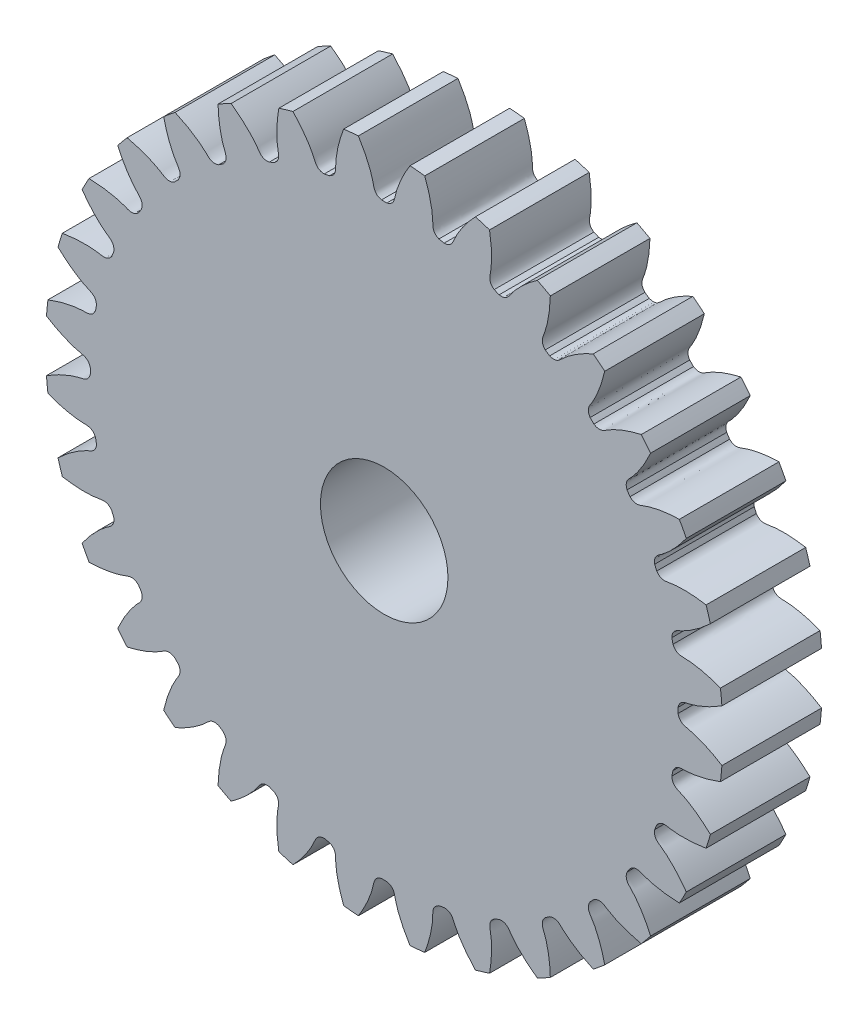
SolidWorks part; units mm, degrees
ref_plane "前视基准面" through (0, 0, 0) normal (0, 0, 1) x (1, 0, 0)
ref_plane "上视基准面" through (0, 0, 0) normal (0, 1, 0) x (1, 0, 0)
ref_plane "右视基准面" through (0, 0, 0) normal (1, 0, 0) x (0, 0, -1)
other "Configuration Table"
sketch "草图1" plane through (0, 0, 0) normal (0, 0, 1) x (1, 0, 0)
  circle A0 centre (0, 0) radius 8.5
extrude "凸台-拉伸1" add sketch "草图1" along normal blind 2.5
ref_axis "基准轴1" through (0, 0, 2.5) along (0, 0, -1)
sketch "草图2" plane through (0, 0, 0) normal (0, 0, 1) x (1, 0, 0)
  line L0 (0, 0) -> (0, 8.5) construction
  circle A0 centre (0, 0) radius 8.5 construction
  arc A1 (0.067, 7.3747) -> (-0.067, 7.3747) centre (0, 0) ccw
  arc A2 (1.6765, 9.6348) -> (-1.6765, 9.6348) centre (0, 0) ccw
  spline S0 degree 3 poles (0.067, 7.3747) (0.2444, 7.4176) (0.2542, 7.5462) (0.2867, 7.6804) (0.2952, 7.7127) (0.3051, 7.7477) (0.3166, 7.7854) (0.3299, 7.8257) (0.3449, 7.8686) (0.3618, 7.9139) (0.3807, 7.9618) (0.4017, 8.012) (0.4249, 8.0645) (0.4505, 8.1193) (0.4785, 8.1763) (0.509, 8.2353) (0.5421, 8.2964) (0.5779, 8.3594) (0.6164, 8.4243) (0.6579, 8.491) (0.7023, 8.5593) (0.7498, 8.6292) (0.8004, 8.7006) (0.8542, 8.7734) (0.9113, 8.8475) (0.9717, 8.9228) (1.0356, 8.9992) (1.1029, 9.0765) (1.1738, 9.1547) (1.2483, 9.2337) (1.3265, 9.3133) (1.4084, 9.3934) (1.5241, 9.5022) (1.6145, 9.5821) (1.6765, 9.6348) knots 0 0 0 0 0.124533 0.135329 0.147193 0.160126 0.174128 0.189198 0.205337 0.222544 0.24082 0.260164 0.280577 0.302059 0.324609 0.348227 0.372914 0.39867 0.425494 0.453386 0.482348 0.512377 0.543476 0.575642 0.608878 0.643181 0.678554 0.714995 0.752504 0.791082 0.830729 0.871444 0.913227 1 1 1 1
  spline S1 degree 3 poles (-0.067, 7.3747) (-0.2444, 7.4176) (-0.2542, 7.5462) (-0.2867, 7.6804) (-0.2952, 7.7127) (-0.3051, 7.7477) (-0.3166, 7.7854) (-0.3299, 7.8257) (-0.3449, 7.8686) (-0.3618, 7.9139) (-0.3807, 7.9618) (-0.4017, 8.012) (-0.4249, 8.0645) (-0.4505, 8.1193) (-0.4785, 8.1763) (-0.509, 8.2353) (-0.5421, 8.2964) (-0.5779, 8.3594) (-0.6164, 8.4243) (-0.6579, 8.491) (-0.7023, 8.5593) (-0.7498, 8.6292) (-0.8004, 8.7006) (-0.8542, 8.7734) (-0.9113, 8.8475) (-0.9717, 8.9228) (-1.0356, 8.9992) (-1.1029, 9.0765) (-1.1738, 9.1547) (-1.2483, 9.2337) (-1.3265, 9.3133) (-1.4084, 9.3934) (-1.5241, 9.5022) (-1.6145, 9.5821) (-1.6765, 9.6348) knots 0 0 0 0 0.124533 0.135329 0.147193 0.160126 0.174128 0.189198 0.205337 0.222544 0.24082 0.260164 0.280577 0.302059 0.324609 0.348227 0.372914 0.39867 0.425494 0.453386 0.482348 0.512377 0.543476 0.575642 0.608878 0.643181 0.678554 0.714995 0.752504 0.791082 0.830729 0.871444 0.913227 1 1 1 1
extrude "切除-拉伸1" cut sketch "草图2" along normal through all
pattern_circular "阵列(圆周)1" count 32 every 11.25 about axis through (0, 0, 2.5) along (0, 0, -1) of "切除-拉伸1"
sketch "草图3" plane through (0, 0, 0) normal (0, 0, 1) x (1, 0, 0)
  circle A0 centre (0, 0) radius 8 construction
  dimension "Dn" = 16
sketch "草图4" plane through (0, 0, 0) normal (0, 0, -1) x (-1, 0, 0)
  circle A0 centre (0, 0) radius 1.6
  dimension "D1" = 3.2
extrude "切除-拉伸2" cut sketch "草图4" against normal up to next
